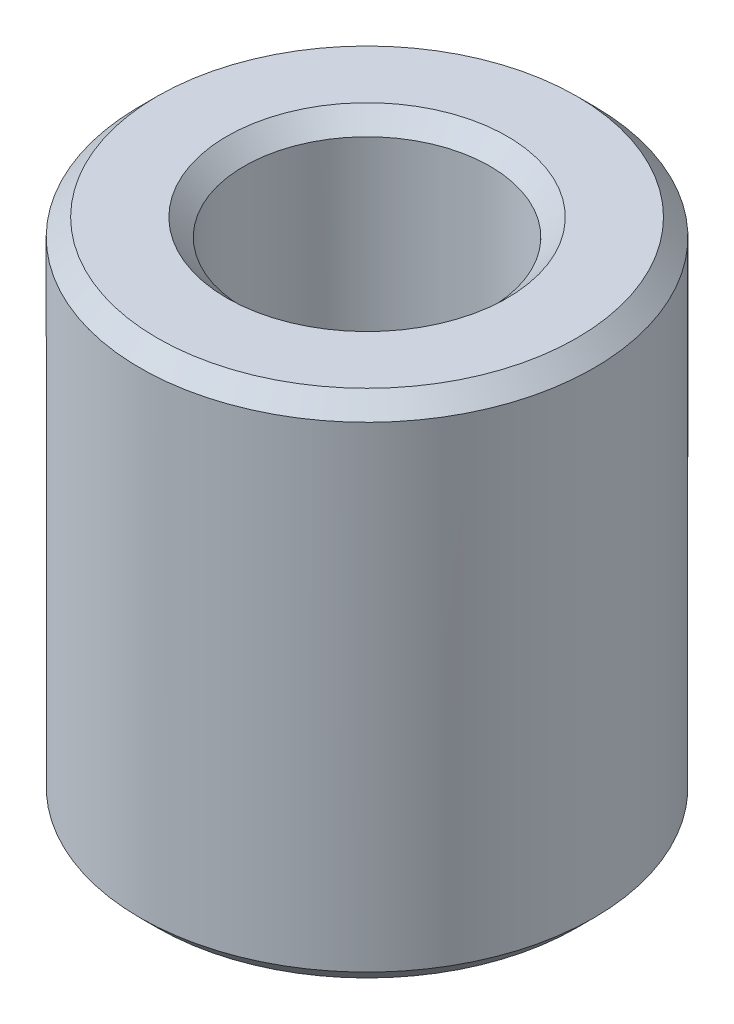
SolidWorks part; units mm, degrees
ref_plane "Front Plane" through (0, 0, 0) normal (0, 0, 1) x (1, 0, 0)
ref_plane "Top Plane" through (0, 0, 0) normal (0, 1, 0) x (1, 0, 0)
ref_plane "Right Plane" through (0, 0, 0) normal (1, 0, 0) x (0, 0, -1)
sketch "Sketch1" plane through (0, 0, 0) normal (0, 1, 0) x (1, 0, 0)
  circle A0 centre (0, 0) radius 12.5
  dimension "SLEEVE_OD" = 25
extrude "Boss-Extrude1" add sketch "Sketch1" along normal blind 28.1367
sketch "Sketch2" plane through (0, 0, 0) normal (0, 1, 0) x (1, 0, 0)
  circle A0 centre (0, 0) radius 6.7709
  dimension "BORE_D" = 13.5417
extrude "Cut-Extrude1" cut sketch "Sketch2" along normal through all
chamfer "Chamfer1" distance 0.9514 angle 45 4 edges at (0, 28.1367, 6.7709) (0, 0, 6.7709) (0, 0, 12.5) (0, 28.1367, 12.5)
